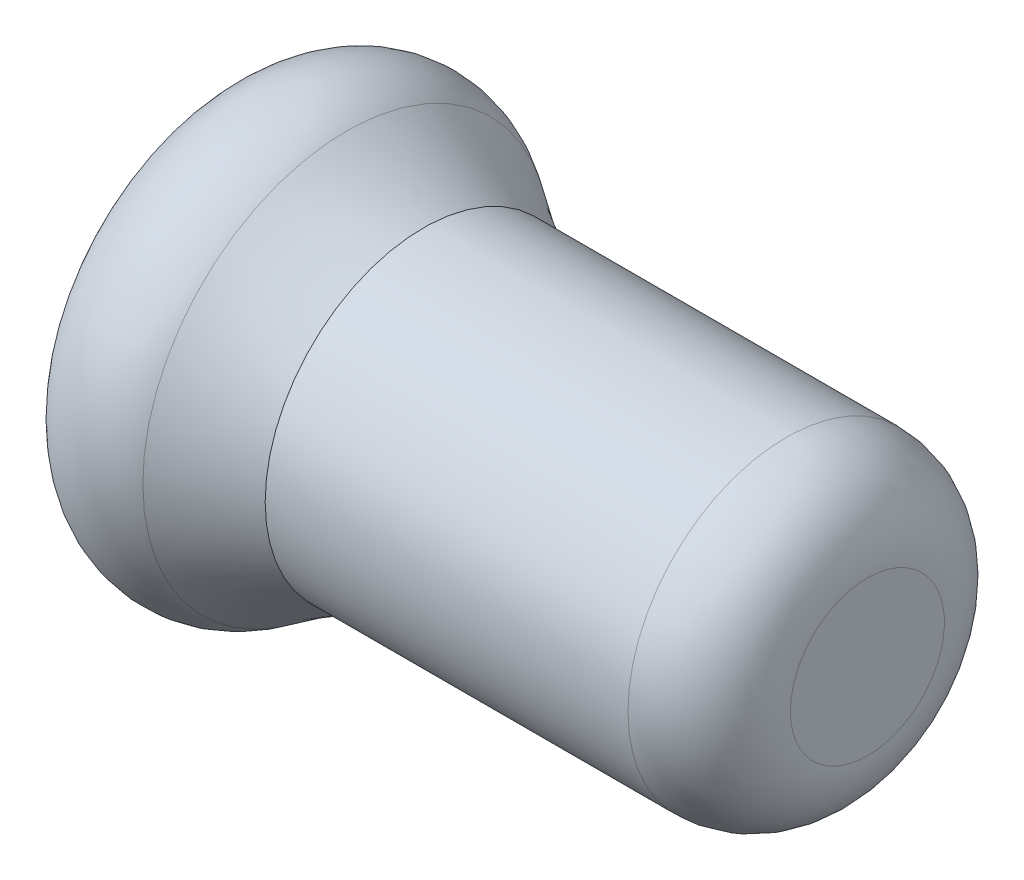
SolidWorks part; units mm, degrees
ref_plane "Front" through (0, 0, 0) normal (0, 0, 1) x (1, 0, 0)
ref_plane "Top" through (0, 0, 0) normal (0, 1, 0) x (1, 0, 0)
ref_plane "Right" through (0, 0, 0) normal (1, 0, 0) x (0, 0, -1)
sketch "Sketch1" plane through (0, 0, 0) normal (0, 0, 1) x (1, 0, 0)
  line L1 (26.6806, 2) -> (26.6806, 0)
  line L2 (26.6806, 0) -> (21.6806, 0)
  line L3 (21.6806, 0) -> (21.6806, 2)
  line L4 (21.6806, 2) -> (-13.3194, 2)
  line L5 (-13.3194, 2) -> (-13.3194, 8.5)
  line L6 (-0.6564, 9.7406) -> (21.6806, 9.7406)
  line L7 (26.6806, 2) -> (26.6806, 4.7406)
  line L8 (-16.0092, 0) -> (32.4976, 0) construction
  arc A0 (-13.3194, 8.5) -> (-5.3835, 12.5473) centre (-8.3194, 8.5) cw
  arc A1 (-5.3835, 12.5473) -> (-0.6564, 9.7406) centre (12.2318, 36.8311) ccw
  arc A2 (21.6806, 9.7406) -> (26.6806, 4.7406) centre (21.6806, 4.7406) cw
  dimension "D6" = 5
  dimension "D8" = 5
  dimension "D1" = 6.5
  dimension "D2" = 35
  dimension "D3" = 5
  dimension "D4" = 2
  dimension "D5" = 2
  dimension "D7" = 30
revolve "Revolve1" add sketch "Sketch1" angle 360 about L8
